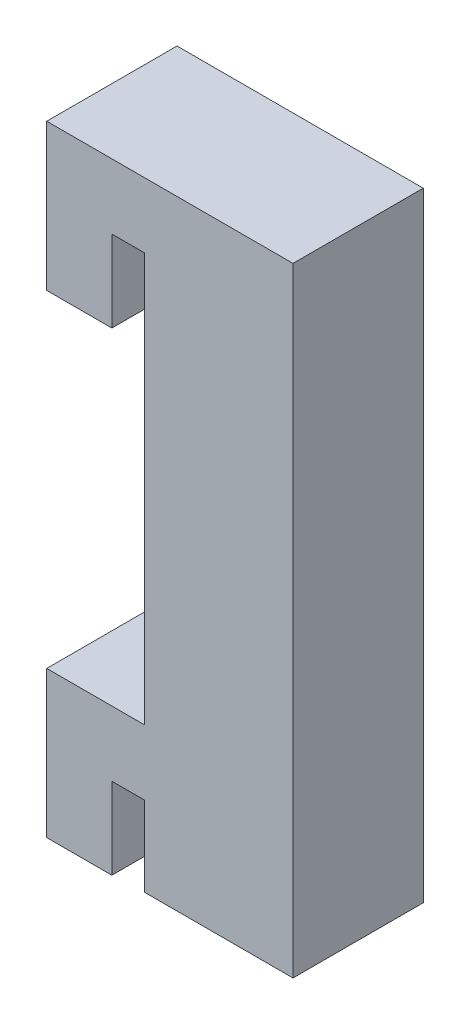
SolidWorks part; units mm, degrees
ref_plane "Plan de face" through (0, 0, 0) normal (0, 0, 1) x (1, 0, 0)
ref_plane "Plan de dessus" through (0, 0, 0) normal (0, 1, 0) x (1, 0, 0)
ref_plane "Plan de droite" through (0, 0, 0) normal (1, 0, 0) x (0, 0, -1)
sketch "Esquisse1" plane through (0, 0, 0) normal (0, 0, 1) x (1, 0, 0)
  line L0 (0, 0) -> (0, 5)
  line L1 (0, 5) -> (2, 5)
  line L4 (2, 0.0964) -> (11.1219, 0.0964)
  line L5 (11.1219, 0.0964) -> (11.1219, 38.1)
  line L8 (11.1219, 38.1) -> (-4, 38.1)
  line L9 (2, 34.1) -> (0, 34.1)
  line L10 (0, 0) -> (-4, 0)
  line L11 (-4, 0) -> (-4, 9)
  line L12 (-4, 9) -> (2, 9)
  line L13 (2, 9) -> (2, 34.1)
  line L14 (0, 34.1) -> (0, 29.1)
  line L15 (0, 29.1) -> (-4, 29.1)
  line L16 (-4, 29.1) -> (-4, 38.1)
  line L17 (2, 5) -> (2, 0.0964)
  point P11 (1, 5)
  dimension "D1" = 29.1
  dimension "D2" = 2
  dimension "D3" = 2
  dimension "D4" = 9
  dimension "D5" = 9
  dimension "D6" = 4
  dimension "D7" = 4
  dimension "D8" = 4
  dimension "D9" = 4
extrude "Boss.-Extru.1" add sketch "Esquisse1" along normal blind 8
